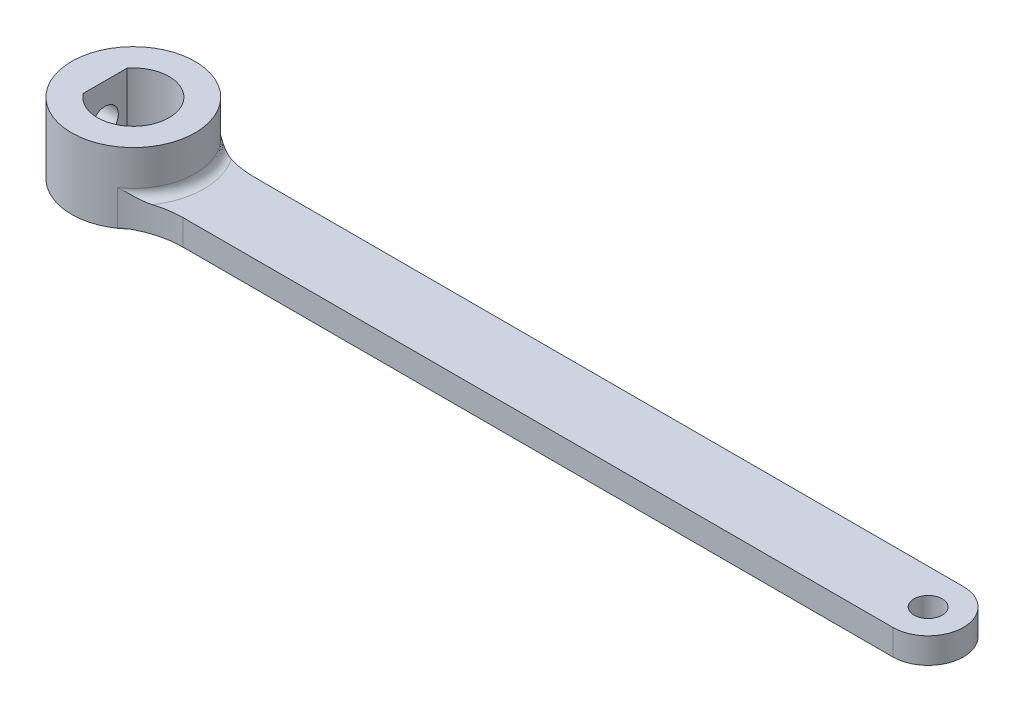
SolidWorks part; units mm, degrees
ref_plane "前视基准面" through (0, 0, 0) normal (0, 0, 1) x (1, 0, 0)
ref_plane "上视基准面" through (0, 0, 0) normal (0, 1, 0) x (1, 0, 0)
ref_plane "右视基准面" through (0, 0, 0) normal (1, 0, 0) x (0, 0, -1)
sketch "Sketch1" plane through (0, 0, 0) normal (0, 1, 0) x (1, 0, 0)
  line L0 (0, 0) -> (90, 0) construction
  line L1 (0, 4) -> (90, 4)
  line L2 (0, -4) -> (90, -4)
  arc A0 (0, 4) -> (0, -4) centre (0, 0) ccw
  arc A1 (90, -4) -> (90, 4) centre (90, 0) ccw
  circle A2 centre (0, 0) radius 1.6
  circle A3 centre (90, 0) radius 1.6
  point P3 (45, 0)
  dimension "D2" = 4
  dimension "D3" = 3.2
  dimension "D4" = 3.2
  dimension "D1" = 90
extrude "Boss-Extrude1" add sketch "Sketch1" along normal blind 2.9
sketch "Sketch2" plane through (0, 2.9, 0) normal (0, 1, 0) x (1, 0, 0)
  circle A0 centre (0, 0) radius 7
  dimension "D1" = 14
extrude "Boss-Extrude2" add sketch "Sketch2" against normal blind 3 and the other way blind 5
sketch "Sketch3" plane through (0, 7.9, 0) normal (0, 1, 0) x (1, 0, 0)
  line L0 (0, 3.7575) -> (0, -4.7435) construction
  line L1 (-3.2, 2.4824) -> (-3.2, -2.4824)
  line L3 (-3.2, 3.7575) -> (-3.2, -4.7435) construction
  arc A0 (-3.2, -2.4824) -> (-3.2, 2.4824) centre (0, 0) ccw
  dimension "D1" = 8.1
  dimension "D2" = 3.2
extrude "Cut-Extrude1" cut sketch "Sketch3" against normal through all
sketch "Sketch4" plane through (-3.2, 0, 0) normal (1, 0, 0) x (0, 0, -1)
  line L0 (0, 7.9) -> (0, 4.9157) construction
  line L1 (4.05, 7.9) -> (-4.05, 7.9) construction
  circle A0 centre (0, 3.9) radius 1.5
  dimension "D1" = 3
  dimension "D2" = 4
extrude "Cut-Extrude2" cut sketch "Sketch4" against normal through all
fillet "Fillet1" radius 10 2 edges at (5.7446, 1.45, 4) (5.7446, 1.45, -4)
fillet "Fillet2" radius 1 1 edges at (7, 2.9, 0)
